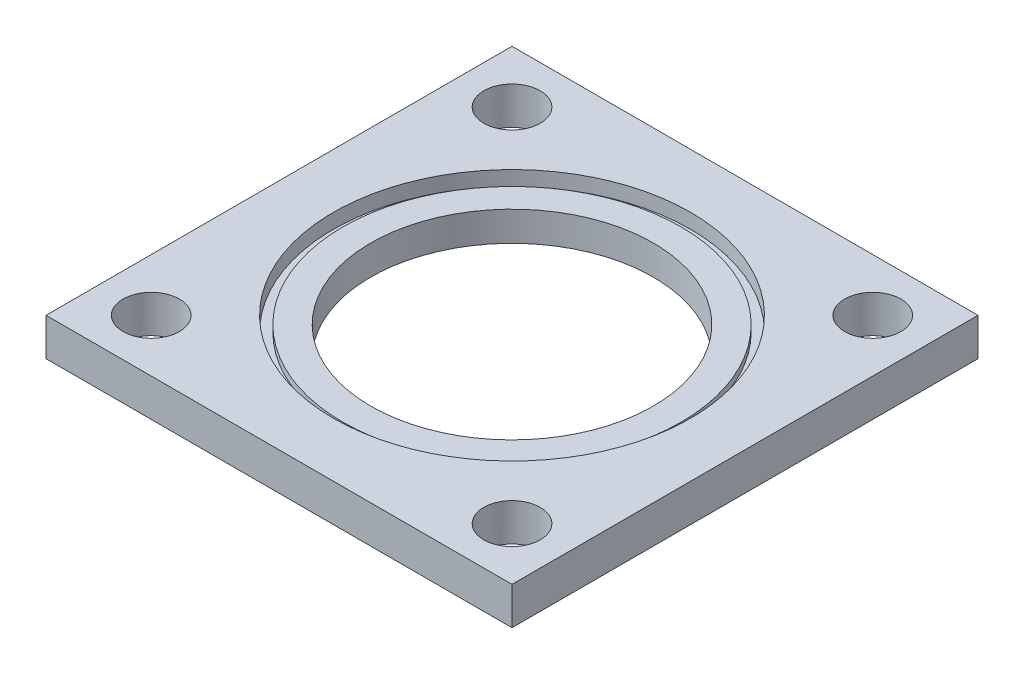
SolidWorks part; units mm, degrees
ref_plane "Front Plane" through (0, 0, 0) normal (0, 0, 1) x (1, 0, 0)
ref_plane "Top Plane" through (0, 0, 0) normal (0, 1, 0) x (1, 0, 0)
ref_plane "Right Plane" through (0, 0, 0) normal (1, 0, 0) x (0, 0, -1)
sketch "plateOutline" plane through (0, 0, 0) normal (0, 1, 0) x (1, 0, 0)
  line L1 (-39.37, -39.37) -> (39.37, -39.37)
  line L2 (-39.37, -39.37) -> (-39.37, 39.37)
  line L3 (-39.37, 39.37) -> (39.37, 39.37)
  line L4 (39.37, -39.37) -> (39.37, 39.37)
  line L5 (-39.37, -39.37) -> (39.37, 39.37) construction
  line L6 (-39.37, 39.37) -> (39.37, -39.37) construction
  line L7 (-39.37, -39.37) -> (39.37, -39.37) construction
  line L8 (-39.37, -39.37) -> (-39.37, 39.37) construction
  line L9 (-39.37, 39.37) -> (39.37, 39.37) construction
  line L10 (39.37, -39.37) -> (39.37, 39.37) construction
  point P0 (0, 0)
  dimension "D1" = 78.74
sketch "railGuides" plane through (0, 0, 0) normal (0, 1, 0) x (1, 0, 0)
  line L0 (-30.48, 30.48) -> (30.48, 30.48) construction
  line L1 (30.48, -30.48) -> (30.48, 30.48) construction
  line L2 (-30.48, -30.48) -> (30.48, -30.48) construction
  line L3 (-30.48, -30.48) -> (-30.48, 30.48) construction
  line L5 (-40.005, -40.005) -> (40.005, -40.005) construction
  line L11 (-40.005, -40.005) -> (-40.005, 40.005) construction
  line L12 (-40.005, 40.005) -> (40.005, 40.005) construction
  line L13 (40.005, -40.005) -> (40.005, 40.005) construction
  line L14 (-40.005, -40.005) -> (40.005, 40.005) construction
  line L15 (-40.005, 40.005) -> (40.005, -40.005) construction
  circle A0 centre (-30.48, 30.48) radius 4.7625
  circle A1 centre (30.48, 30.48) radius 4.7625
  circle A2 centre (30.48, -30.48) radius 4.7625
  circle A3 centre (-30.48, -30.48) radius 4.7625
  point P1 (0, 0)
  dimension "D1" = 80.01
  dimension "D3" = 9.525
  dimension "D4" = 9.525
  dimension "D5" = 9.525
  dimension "D6" = 9.525
  dimension "D7" = 9.525
  dimension "D2" = 80.01
sketch "FuelGrainMounting" plane through (0, 0, 0) normal (0, 1, 0) x (1, 0, 0)
  circle A0 centre (0, 0) radius 30.1625
  dimension "D1" = 60.325
sketch "GasIntake" plane through (0, 0, 0) normal (0, 1, 0) x (1, 0, 0)
  line L0 (-39.37, 39.37) -> (39.37, -39.37) construction
  circle A0 centre (0, 0) radius 23.876
  dimension "D1" = 47.752
extrude "Boss-Extrude1" add sketch "plateOutline" along normal blind 6.35 contours L3 L4 L1 L2
extrude "Cut-Extrude1" cut sketch "railGuides" along normal blind 10 contours A0 | A3 | A1 | A2 region at (-30.48, 0, -30.48)
extrude "Cut-Extrude2" cut sketch "FuelGrainMounting" along normal blind 5 from offset 5
extrude "Cut-Extrude3" cut sketch "GasIntake" along normal blind 5
sketch "Sketch1" plane through (0, 0, 0) normal (0, 1, 0) x (1, 0, 0)
  circle A0 centre (0, 0) radius 28.575
  circle A2 centre (0, 0) radius 30.1625
  dimension "D1" = 60.325
  dimension "D2" = 57.15
extrude "Cut-Extrude4" cut sketch "Sketch1" against normal blind 1.143 from offset 5
